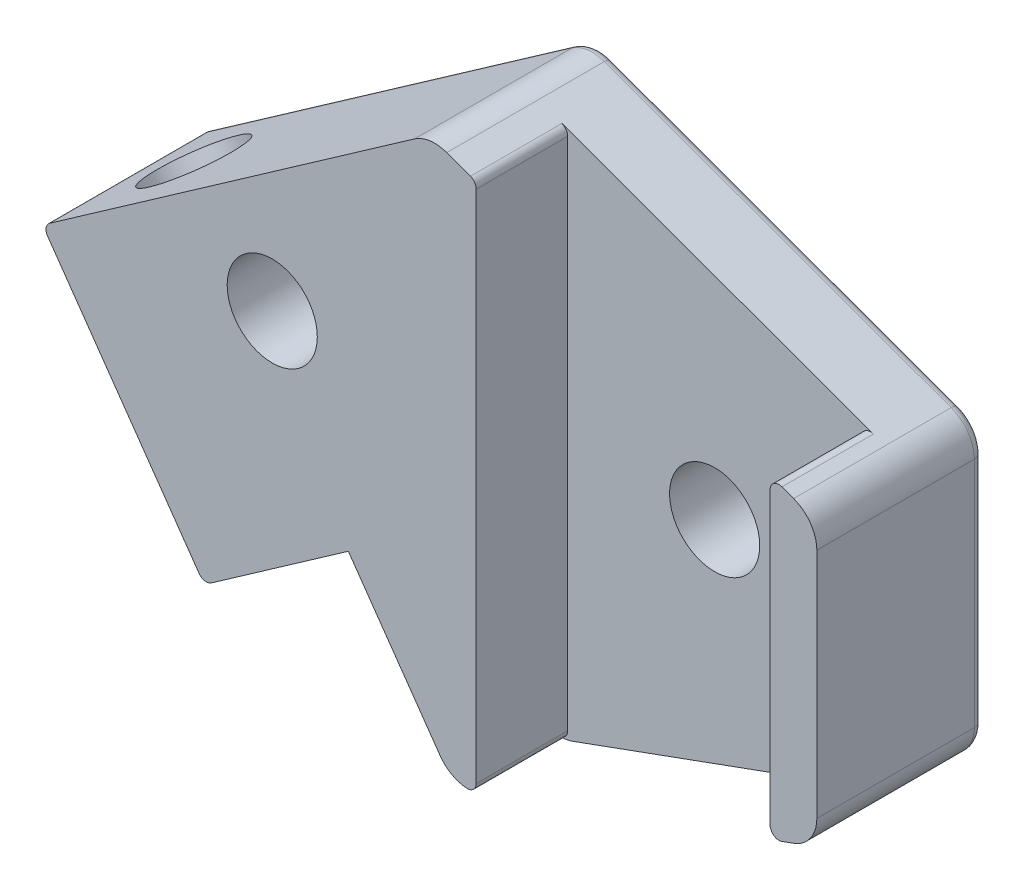
SolidWorks part; units mm, degrees
ref_plane "Front Plane" through (0, 0, 0) normal (0, 0, 1) x (1, 0, 0)
ref_plane "Top Plane" through (0, 0, 0) normal (0, 1, 0) x (1, 0, 0)
ref_plane "Right Plane" through (0, 0, 0) normal (1, 0, 0) x (0, 0, -1)
sketch "Sketch1" plane through (0, 0, 0) normal (0, 0, 1) x (1, 0, 0)
  line L0 (-11.6417, 0) -> (-2.9104, 0) construction
  line L1 (5.8208, -6.35) -> (-11.6417, -12.7)
  line L2 (5.8208, -6.35) -> (5.8208, 6.35)
  line L3 (5.8208, 6.35) -> (-11.6417, 12.7)
  line L4 (-11.6417, -12.7) -> (-11.6417, 12.7)
  line L5 (5.8208, -6.35) -> (-11.6417, 12.7) construction
  line L6 (5.8208, 6.35) -> (-11.6417, -12.7) construction
  line L7 (-2.9104, 0) -> (5.8208, 0) construction
  circle A0 centre (-2.9104, 0) radius 2.032
  point P0 (0, 0)
  dimension "D2" = 4.064
  dimension "D1" = 17.4625
  dimension "D3" = 12.7
  dimension "D4" = 25.4
extrude "Boss-Extrude1" add sketch "Sketch1" along normal blind 3.375
sketch "Sketch2" plane through (0, 0, 3.375) normal (0, 0, 1) x (1, 0, 0)
  line L0 (-11.6417, -12.7) -> (5.8208, -6.35) construction
  line L2 (-11.6417, 12.7) -> (-11.6417, -12.7)
  line L4 (-9.5354, 11.9341) -> (-9.5354, -11.9341)
  line L5 (5.8208, 6.35) -> (-11.6417, 12.7) construction
  line L7 (5.8208, 6.35) -> (5.8208, -6.35)
  line L9 (3.7146, 7.1159) -> (3.7146, -7.1159)
  line L10 (-11.6417, -12.7) -> (-9.5354, -11.9341)
  line L11 (5.8208, 6.35) -> (3.7146, 7.1159)
  line L12 (3.7146, -7.1159) -> (5.8208, -6.35)
  line L13 (-9.5354, 11.9341) -> (-11.6417, 12.7)
  circle A0 centre (-2.9104, 0) radius 6.625 construction
  dimension "D2" = 13.25
extrude "Boss-Extrude2" add sketch "Sketch2" along normal blind 4.125
sketch "Sketch4" plane through (0, 0, 0) normal (0, 0, -1) x (-1, 0, 0)
  line L0 (11.6417, 12.7) -> (29.0879, 0.484)
  line L2 (21.8035, -9.9192) -> (11.6417, -12.7)
  line L3 (11.6417, -12.7) -> (11.6417, 12.7)
  line L4 (29.0879, 0.484) -> (21.8035, -9.9192)
  circle A0 centre (18.7325, 2.3012) radius 2.032
  circle A1 centre (2.9104, 0) radius 2.032 construction
  point P9 (25.5679, -5.3405)
  dimension "D1" = 18.7325
  dimension "D2" = 2.3012
  dimension "D3" = 35
  dimension "D4" = 9.525
  dimension "D5" = 12.7
extrude "Boss-Extrude3" add sketch "Sketch4" against normal up to surface (7.5 mm away) up to face at (-10.5885, 0, 7.5)
sketch "Sketch5" plane through (-9.797, 13.9916, 0) normal (-0.5736, 0.8192, 0) x (0.8192, 0.5736, 0)
  line L0 (-23.5498, -3.75) -> (-19.7998, -3.75) construction
  line L1 (-23.5498, -7.5) -> (-23.5498, 0) construction
  line L2 (-19.7998, -3.75) -> (-19.7998, 0) construction
  line L3 (-23.5498, 0) -> (-2.2519, 0) construction
  circle A0 centre (-19.7998, -3.75) radius 2.032
  dimension "D1" = 4.064
extrude "Cut-Extrude1" cut sketch "Sketch5" against normal through all
ref_plane "Plane1" through (-2.5126, 3.5884, 0) normal (-0.5736, 0.8192, 0) x (0.8192, 0.5736, 0)
sketch "Sketch6" plane through (-2.5126, 3.5884, 0) normal (-0.5736, 0.8192, 0) x (0.8192, 0.5736, 0)
  line L0 (-15.6123, -7.5) -> (-15.6123, 0)
  line L1 (-23.5498, -7.5) -> (-2.2519, -7.5) construction
  line L2 (-23.5498, 0) -> (-2.2519, 0) construction
  line L3 (-15.6123, 0) -> (-23.5498, 0)
  line L4 (-23.5498, 0) -> (-23.5498, -7.5)
  line L5 (-23.5498, -7.5) -> (-15.6123, -7.5)
  dimension "D1" = 7.9375
extrude "Cut-Extrude2" cut sketch "Sketch6" against normal through all
fillet "Fillet1" radius 1.5875 4 edges at (5.8208, -6.35, 3.75) (5.8208, 6.35, 3.75) (-11.6417, 12.7, 3.75) (-10.4659, -12.2724, 3.75)
fillet "Fillet2" radius 0.3969 17 edges at (3.7146, -7.1159, 5.4375) (3.7146, 7.1159, 5.4375) (5.5336, 6.1488, 0) (5.8208, 0, 0) (5.5336, -6.1488, 0) (-2.2728, -9.2931, 0) (-3.0447, 9.5738, 0) (-13.2329, -8.3207, 0) (-20.7031, 6.3551, 0) (-11.6153, 12.4997, 0) (-18.5525, -7.6429, 0) (-25.4457, -4.7176, 0) (-29.0879, 0.484, 3.75) (-21.8035, -9.9192, 3.75) (-9.5354, 11.9341, 5.4375) (-10.3415, -11.8783, 0) (-9.5354, -11.9175, 5.4375)
